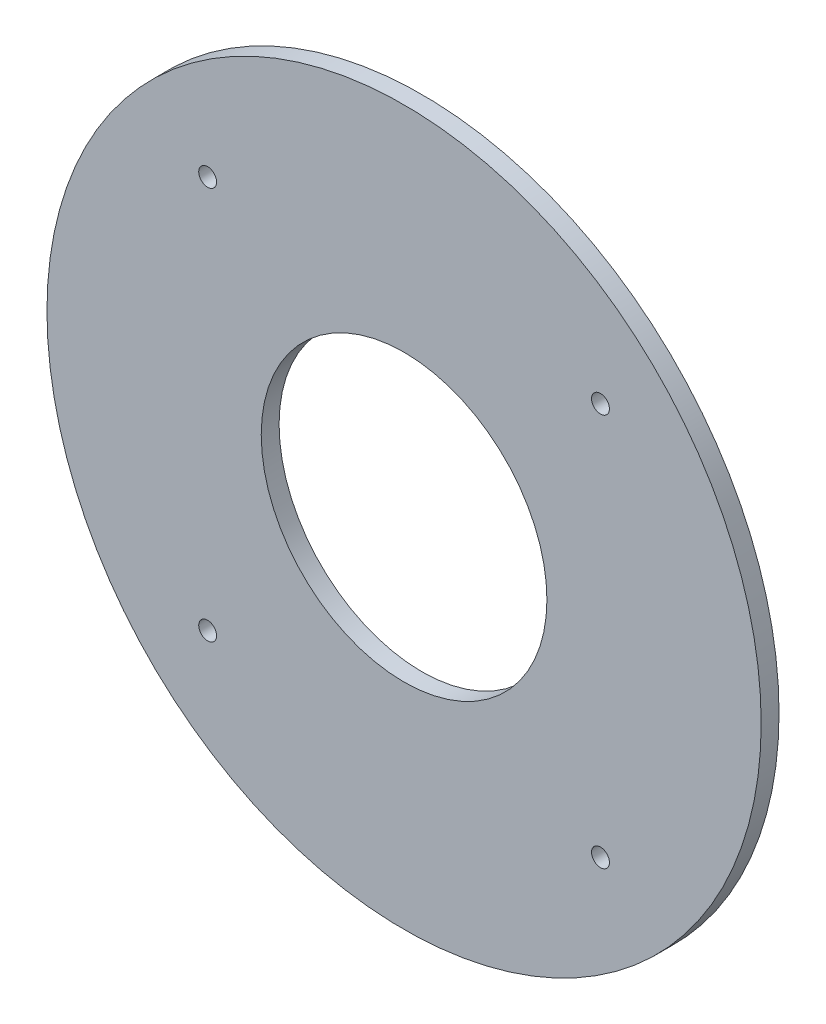
SolidWorks part; units mm, degrees
material "Pine"
ref_plane "Front Plane" through (0, 0, 0) normal (0, 0, 1) x (1, 0, 0)
ref_plane "Top Plane" through (0, 0, 0) normal (0, 1, 0) x (1, 0, 0)
ref_plane "Right Plane" through (0, 0, 0) normal (1, 0, 0) x (0, 0, -1)
sketch "Sketch1" plane through (0, 0, 0) normal (0, 0, 1) x (1, 0, 0)
  circle A0 centre (0, 0) radius 50.8
  circle A1 centre (0, 0) radius 127
  circle A2 centre (-69.85, 69.85) radius 3.175 construction
  circle A3 centre (-69.85, 69.85) radius 3.175
  circle A4 centre (69.85, 69.85) radius 3.175 construction
  circle A5 centre (69.85, 69.85) radius 3.175
  circle A6 centre (-69.85, -69.85) radius 3.175 construction
  circle A7 centre (69.85, -69.85) radius 3.175 construction
  circle A8 centre (-69.85, -69.85) radius 3.175
  circle A9 centre (69.85, -69.85) radius 3.175
  dimension "D1" = 101.6
  dimension "D2" = 254
extrude "Boss-Extrude1" add sketch "Sketch1" along normal blind 6.35
